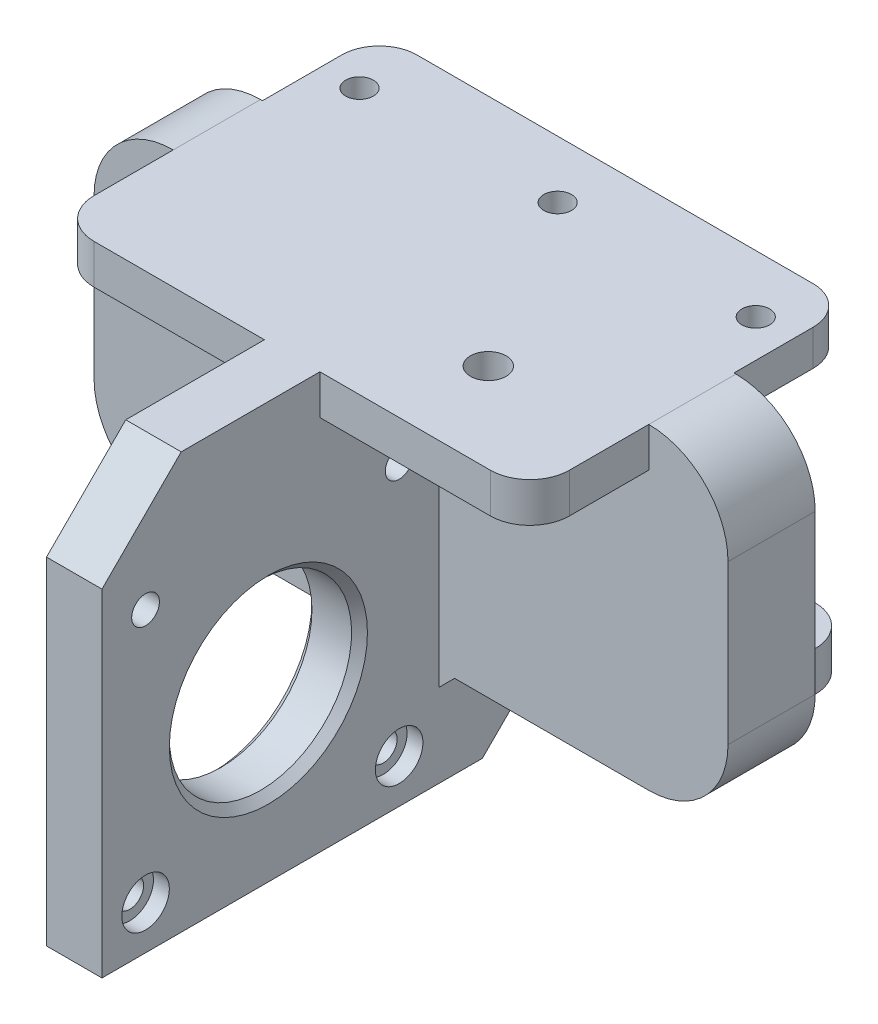
SolidWorks part; units mm, degrees
ref_plane "Front Plane" through (0, 0, 0) normal (0, 0, 1) x (1, 0, 0)
ref_plane "Top Plane" through (0, 0, 0) normal (0, 1, 0) x (1, 0, 0)
ref_plane "Right Plane" through (0, 0, 0) normal (1, 0, 0) x (0, 0, -1)
sketch "Sketch1" plane through (0, 0, 0) normal (0, 0, 1) x (1, 0, 0)
  line L0 (60, 35) -> (0, 35)
  line L1 (0, 35) -> (0, 40)
  line L2 (-10, 30) -> (-10, 10)
  line L3 (0, 0) -> (60, 0)
  line L4 (70, 10) -> (70, 30)
  line L5 (60, 40) -> (60, 35)
  arc A0 (0, 40) -> (-10, 30) centre (0, 30) ccw
  arc A1 (-10, 10) -> (0, 0) centre (0, 10) ccw
  arc A2 (60, 0) -> (70, 10) centre (60, 10) ccw
  arc A3 (70, 30) -> (60, 40) centre (60, 30) ccw
extrude "Boss-Extrude1" add sketch "Sketch1" along normal blind 11
sketch "Sketch2" plane through (0, 0, 11) normal (0, 0, 1) x (1, 0, 0)
  line L1 (0, 35) -> (60, 35)
  line L2 (0, 35) -> (0, 40)
  line L3 (0, 40) -> (60, 40)
  line L4 (60, 35) -> (60, 40)
extrude "Boss-Extrude2" add sketch "Sketch2" against normal blind 26
fillet "Fillet1" radius 5 2 edges at (60, 37.5, -15) (0, 37.5, -15)
sketch "Sketch4" plane through (0, 35, 0) normal (0, -1, 0) x (-1, 0, 0)
  line L0 (-55, 15) -> (-55, 7.5) construction
  line L1 (-30, 15) -> (-30, 7.5) construction
  line L2 (-5, 15) -> (-55, 15) construction
  line L3 (-5, 15) -> (-5, 7.5) construction
  arc A0 (0, 10) -> (-5, 15) centre (-5, 10) ccw construction
  circle A1 centre (-55, 7.5) radius 1.75
  circle A2 centre (-30, 7.5) radius 1.75
  circle A3 centre (-5, 7.5) radius 1.75
  dimension "D2" = 3.5
  dimension "D1" = 7.5
extrude "Cut-Extrude2" cut sketch "Sketch4" against normal blind 25
sketch "Sketch5" plane through (0, 35, 0) normal (0, -1, 0) x (1, 0, 0)
  line L0 (5, -14.75) -> (55, -14.75)
  line L1 (59.75, -10) -> (59.75, -0.25)
  line L3 (0.25, -0.25) -> (0.25, -10)
  line L4 (5, -15) -> (55, -15)
  line L5 (60, -10) -> (60, 0)
  line L6 (60, 0) -> (0, 0)
  line L7 (0, 0) -> (0, -10)
  line L8 (5, -15) -> (55, -15)
  line L9 (60, -10) -> (60, 0)
  line L10 (60, 0) -> (59.75, 0)
  line L11 (0, 0) -> (0, -10)
  line L12 (59.75, -0.25) -> (59.75, 0)
  line L13 (0.25, -0.25) -> (0.25, 0)
  line L14 (0.25, 0) -> (0, 0)
  line L16 (60, 0) -> (0, 0) construction
  line L17 (59.75, -0.25) -> (0.25, -0.25) construction
  arc A0 (55, -14.75) -> (59.75, -10) centre (55, -10) ccw
  arc A1 (0.25, -10) -> (5, -14.75) centre (5, -10) ccw
  arc A2 (55, -15) -> (60, -10) centre (55, -10) ccw
  arc A3 (0, -10) -> (5, -15) centre (5, -10) ccw
  arc A4 (55, -15) -> (60, -10) centre (55, -10) ccw
  arc A5 (0, -10) -> (5, -15) centre (5, -10) ccw
  dimension "D1" = 0
  dimension "D2" = 0.25
extrude "Cut-Extrude3" cut sketch "Sketch5" against normal blind 25
sketch "Sketch6" plane through (0, 0, 11) normal (0, 0, 1) x (1, 0, 0)
  line L1 (60, 40) -> (0, 40)
  line L2 (60, 40) -> (60, 35)
  line L3 (60, 35) -> (0, 35)
  line L4 (0, 40) -> (0, 35)
  dimension "D1" = 5
extrude "Boss-Extrude3" add sketch "Sketch6" along normal blind 15
fillet "Fillet2" radius 5 2 edges at (0, 37.5, 26) (60, 37.5, 26)
sketch "Sketch7" plane through (0, 0, 11) normal (0, 0, 1) x (1, 0, 0)
  line L0 (0, 35) -> (60, 35) construction
  line L1 (33.5, 35) -> (26.5, 35)
  line L2 (33.5, 35) -> (33.5, -10)
  line L3 (33.5, -10) -> (26.5, -10)
  line L4 (26.5, 35) -> (26.5, -10)
  line L5 (0, 0) -> (60, 0) construction
  point P6 (30, -10)
  point P9 (30, 0)
  dimension "D1" = 0
  dimension "D2" = 7
  dimension "D3" = 45
extrude "Boss-Extrude4" add sketch "Sketch7" along normal blind 42.5
ref_plane "Plane1" through (0, 20, 0) normal (0, -1, 0) x (-1, 0, 0)
mirror "Mirror1" about plane through (0, 20, 0) normal (0, -1, 0) of "Cut-Extrude2", "Fillet1", "Boss-Extrude2"
sketch "Sketch8" plane through (26.5, 0, 0) normal (-1, 0, 0) x (0, 0, 1)
  line L0 (53.5, -10) -> (11, -10) construction
  line L2 (11, 35) -> (11, 0) construction
  line L3 (32.5, 8.4983) -> (48, -7.0017) construction
  line L4 (53.5, 35) -> (26, 35) construction
  circle A0 centre (32.5, 8.4983) radius 11.5
  circle A1 centre (48, -7.0017) radius 1.75
  circle A2 centre (16, -7.0017) radius 1.75
  circle A3 centre (16, 24.9983) radius 1.75
  circle A4 centre (48, 24.9983) radius 1.75
  point P3 (32.25, -10)
  point P21 (32, 8.9983)
  dimension "D1" = 23
  dimension "D6" = 3.5
  dimension "D2" = 18.5
  dimension "D3" = 21.5
  dimension "D4" = 45
  dimension "D5" = 15.5
  dimension "D7" = 4
extrude "Cut-Extrude4" cut sketch "Sketch8" against normal blind 42
sketch "Sketch11" plane through (0, -10, 0) normal (0, -1, 0) x (-1, 0, 0)
  line L1 (-26.5, -53.5) -> (-33.5, -53.5)
  line L2 (-26.5, -53.5) -> (-26.5, -11)
  line L3 (-26.5, -11) -> (-33.5, -11)
  line L4 (-33.5, -53.5) -> (-33.5, -11)
extrude "Boss-Extrude6" add sketch "Sketch11" along normal blind 2.5
chamfer "Chamfer8" distance 5 angle 45 1 edges at (30, 35, 53.5)
sketch "Sketch12" plane through (33.5, 0, 0) normal (1, 0, 0) x (0, 0, -1)
  line L0 (-48.5, 35) -> (-26, 35)
  line L1 (-26, 35) -> (-26, 40)
  line L2 (-26, 40) -> (-43.5, 40)
  line L3 (-43.5, 40) -> (-48.5, 35)
  line L4 (-48.5, 35) -> (-53.5, 30) construction
extrude "Boss-Extrude7" add sketch "Sketch12" against normal up to surface (7 mm away) up to face at (26.5, -8.7517, 48)
sketch "Sketch13" plane through (0, 0, 0) normal (0, -1, 0) x (1, 0, 0)
  line L0 (55, -15) -> (5, -15) construction
  line L1 (26.5, 11) -> (33.5, 11)
  line L2 (26.5, 11) -> (26.5, -3.9293)
  line L3 (26.5, -15) -> (33.5, -15)
  line L4 (33.5, 11) -> (33.5, -3.9293)
  line L5 (33.5, -11.0707) -> (33.5, -15)
  line L6 (26.5, -11.0707) -> (26.5, -15)
  circle A0 centre (30, -7.5) radius 1.75
  arc A1 (33.5, -11.0707) -> (33.5, -3.9293) centre (30, -7.5) ccw
  arc A2 (26.5, -3.9293) -> (26.5, -11.0707) centre (30, -7.5) ccw
  dimension "D1" = 5
extrude "Boss-Extrude8" add sketch "Sketch13" along normal blind 5
chamfer "Chamfer9" distance 13 angle 45 1 edges at (30, -5, 11)
chamfer "Chamfer10" distance 3 angle 45 1 edges at (30, -5, -15)
sketch "Sketch14" plane through (0, -5, 0) normal (0, -1, 0) x (-1, 0, 0)
  circle A0 centre (-30, 7.5) radius 3
  dimension "D1" = 6
extrude "Cut-Extrude5" cut sketch "Sketch14" against normal blind 5
chamfer "Chamfer11" distance 2 angle 45 2 edges at (33.5, 0, 3.5354) (26.5, 0, 3.5354)
sketch "Sketch15" plane through (33.5, 0, 0) normal (1, 0, 0) x (0, 0, -1)
  circle A0 centre (-16, -7.0017) radius 3
  circle A1 centre (-48, -7.0017) radius 3
  dimension "D1" = 6
  dimension "D2" = 6
extrude "Cut-Extrude6" cut sketch "Sketch15" against normal blind 2
chamfer "Chamfer12" distance 1 angle 45 2 edges at (26.5, -3.0017, 32.5) (33.5, -3.0017, 32.5)
sketch "Sketch16" plane through (0, 35, 0) normal (0, -1, 0) x (1, 0, 0)
  line L4 (0.25, 0) -> (0.25, -10)
  line L5 (5, -14.75) -> (55, -14.75)
  line L6 (59.75, -10) -> (59.75, 0)
  line L7 (59.75, 0) -> (0.25, 0)
  line L8 (0.25, 0) -> (0.25, -10)
  line L9 (5, -14.75) -> (55, -14.75)
  line L10 (59.75, -10) -> (59.75, 0)
  line L11 (59.75, 0) -> (0.25, 0)
  arc A2 (0.25, -10) -> (5, -14.75) centre (5, -10) ccw
  arc A3 (55, -14.75) -> (59.75, -10) centre (55, -10) ccw
  arc A4 (0.25, -10) -> (5, -14.75) centre (5, -10) ccw
  arc A5 (55, -14.75) -> (59.75, -10) centre (55, -10) ccw
  dimension "D1" = 0
extrude "Cut-Extrude7" cut sketch "Sketch16" against normal blind 0.5
sketch "Sketch17" plane through (0, 0, 0) normal (0, 0, -1) x (-1, 0, 0)
  line L0 (8, 10) -> (8, 30)
  line L1 (0, 5) -> (-0.25, 35.5)
  line L2 (0, 38) -> (-0.25, 38)
  line L10 (0, 5) -> (0, 0)
  line L11 (10, 10) -> (10, 30)
  line L12 (0, 40) -> (-0.25, 40)
  line L13 (-0.25, 40) -> (-0.25, 35.5)
  line L14 (-0.25, 35.5) -> (-59.75, 35.5)
  line L15 (-59.75, 35.5) -> (-59.75, 40)
  line L16 (-59.75, 40) -> (-60, 40)
  line L17 (-70, 30) -> (-70, 10)
  line L18 (-60, 0) -> (-60, 5)
  line L19 (-60, 5) -> (0, 5)
  line L20 (0, 5) -> (0, 2)
  line L23 (-0.25, 38) -> (-0.25, 35.5)
  line L24 (-0.25, 35.5) -> (-59.75, 35.5)
  line L25 (-59.75, 35.5) -> (-59.75, 40)
  line L26 (-59.75, 40) -> (-60, 40)
  line L27 (-70, 30) -> (-70, 10)
  line L28 (-60, 0) -> (-60, 5)
  line L29 (-60, 5) -> (0, 5)
  arc A0 (0, 2) -> (8, 10) centre (0, 10) ccw
  arc A1 (8, 30) -> (0, 38) centre (0, 30) ccw
  arc A4 (0, 0) -> (10, 10) centre (0, 10) ccw
  arc A5 (10, 30) -> (0, 40) centre (0, 30) ccw
  arc A6 (-60, 40) -> (-70, 30) centre (-60, 30) ccw
  arc A7 (-70, 10) -> (-60, 0) centre (-60, 10) ccw
  arc A10 (-60, 40) -> (-70, 30) centre (-60, 30) ccw
  arc A11 (-70, 10) -> (-60, 0) centre (-60, 10) ccw
  line M15 (0, 5) -> (0, 0)
  line M20 (-0.25, 40) -> (-0.25, 35.5)
  dimension "D1" = 0
extrude "Cut-Extrude8" cut sketch "Sketch17" against normal offset from surface (9 mm away) 2 contours L0 A1 L2 L1 A0 M20 M15 region at (-3.7021, 20.1162, 0) up to face at (6.6697, 18.5, 11)
ref_plane "Plane2" through (30, 0, 0) normal (1, 0, 0) x (0, 0, -1)
mirror "Mirror2" about plane through (30, 0, 0) normal (1, 0, 0) of "Cut-Extrude8"
sketch "Sketch18" plane through (0, 35, 0) normal (0, -1, 0) x (1, 0, 0)
  circle A0 centre (43.5, 14.7517) radius 2.25
  dimension "D1" = 4.5
extrude "Cut-Extrude9" cut sketch "Sketch18" against normal blind 10
